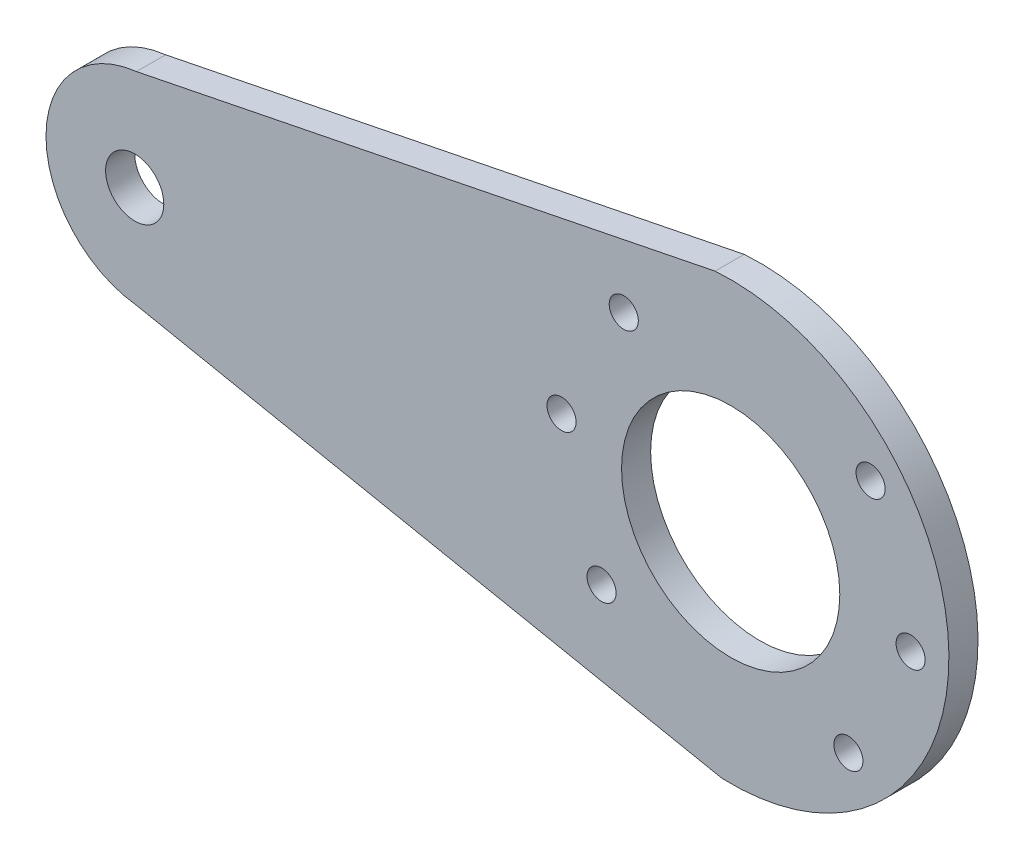
SolidWorks part; units mm, degrees
ref_plane "Спереди" through (0, 0, 0) normal (0, 0, 1) x (1, 0, 0)
ref_plane "Сверху" through (0, 0, 0) normal (0, 1, 0) x (1, 0, 0)
ref_plane "Справа" through (0, 0, 0) normal (1, 0, 0) x (0, 0, -1)
sketch "Эскиз1" plane through (0, 0, 0) normal (0, 0, 1) x (1, 0, 0)
  line L0 (0, 0) -> (-76.7265, 0) construction
  line L1 (-81.6768, 13.912) -> (-2.138, 29.9237)
  line L2 (-81.7023, -13.9091) -> (-1.2006, -29.976)
  circle A0 centre (0, 0) radius 15
  arc A1 (-1.2006, -29.976) -> (-2.138, 29.9237) centre (0, 0) ccw
  arc A2 (-81.6768, 13.912) -> (-81.7023, -13.9091) centre (-80.1094, 0) ccw
  circle A4 centre (-81.9176, 0) radius 4
extrude "Вытянуть1" add sketch "Эскиз1" along normal blind 4 from offset 2 offset against normal yes
sketch "Эскиз2" plane through (0, 0, 2) normal (0, 0, 1) x (1, 0, 0)
  circle A0 centre (-17.747, -15.2052) radius 2
  circle A1 centre (-23.2474, 2.391) radius 2
  circle A2 centre (-14.6943, 18.7227) radius 2
  circle A4 centre (19.2336, 15.6699) radius 2
  circle A5 centre (24.734, -1.9263) radius 2
  circle A6 centre (16.1809, -18.258) radius 2
  circle A8 centre (-1.4153, -23.7583) radius 2 [skipped]
  circle A9 centre (2.9019, 24.223) radius 2 [skipped]
extrude "Вырез-Вытянуть1" cut sketch "Эскиз2" against normal through all
